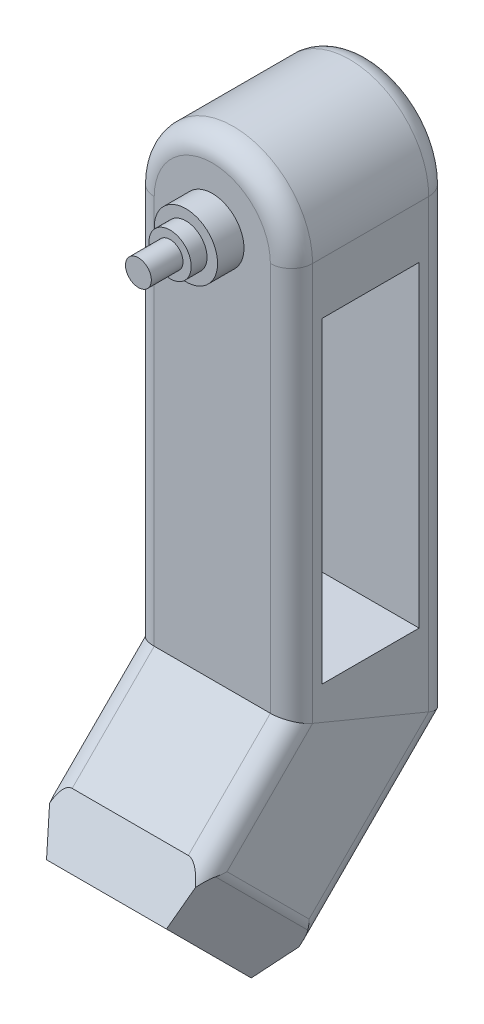
SolidWorks part; units mm, degrees
ref_plane "Front Plane" through (0, 0, 0) normal (0, 0, 1) x (1, 0, 0)
ref_plane "Top Plane" through (0, 0, 0) normal (0, 1, 0) x (1, 0, 0)
ref_plane "Right Plane" through (0, 0, 0) normal (1, 0, 0) x (0, 0, -1)
ref_plane "Plane2" through (0, 96.393, 0) normal (0, 1, 0) x (1, 0, 0)
sketch "Sketch10" plane through (0, 0, 0) normal (1, 0, 0) x (0, 0, -1)
  line L0 (0, 96.393) -> (0, -5.207)
  line L1 (55, 96.393) -> (-55, 96.393) construction
  line L2 (0, -5.207) -> (-25.3243, -30.5313)
  dimension "D1" = 101.6
  dimension "D2" = 35.814
  dimension "D3" = 135
sketch "Sketch11" plane through (0, 96.393, 0) normal (0, 1, 0) x (1, 0, 0)
  line L1 (-19.05, -19.05) -> (19.05, -19.05)
  line L2 (-19.05, -19.05) -> (-19.05, 19.05)
  line L3 (-19.05, 19.05) -> (19.05, 19.05)
  line L4 (19.05, -19.05) -> (19.05, 19.05)
  line L5 (-19.05, -19.05) -> (19.05, 19.05) construction
  line L6 (-19.05, 19.05) -> (19.05, -19.05) construction
  point P0 (0, 0)
  dimension "D1" = 38.1
sweep "Sweep1" add profiles "Sketch11" path "Sketch10"
sketch "Sketch12" plane through (0, -27.9278, 27.9278) normal (0, -0.7071, 0.7071) x (1, 0, 0)
  line L4 (19.05, -22.7319) -> (19.05, 15.3681)
  line L5 (19.05, -22.7319) -> (19.05, 15.3681)
  line L6 (19.05, 15.3681) -> (-19.05, 15.3681)
  line L7 (19.05, 15.3681) -> (-19.05, 15.3681)
  line L8 (-19.05, 15.3681) -> (-19.05, -22.7319)
  line L9 (-19.05, 15.3681) -> (-19.05, -22.7319)
  line L10 (-19.05, -22.7319) -> (19.05, -22.7319)
  line L11 (-19.05, -22.7319) -> (19.05, -22.7319)
  dimension "D1" = 0
extrude "Boss-Extrude5" add sketch "Sketch12" along normal blind 12.7 draft 20
sketch "Sketch13" plane through (0, 0, -19.05) normal (0, 0, -1) x (-1, 0, 0)
  line L0 (20.955, 96.393) -> (-20.955, 96.393) construction
  line L1 (0, 31.8146) -> (0, -31.8146) construction
  line L2 (-19.05, 96.393) -> (19.05, 96.393)
  arc A0 (19.05, 96.393) -> (-19.05, 96.393) centre (0, 96.393) ccw
  dimension "D1" = 38.1
extrude "Boss-Extrude6" add sketch "Sketch13" against normal up to surface (38.1 mm away) up to face at (0, 49.5384, 19.05)
sketch "Sketch15" plane through (0, -36.9081, 36.9081) normal (0, -0.7071, 0.7071) x (1, 0, 0)
  line L1 (-14.4276, 10.7457) -> (14.4276, -18.1095) construction
  line L2 (-14.4276, -18.1095) -> (14.4276, 10.7457) construction
  circle A2 centre (0, -3.6819) radius 12.065
  dimension "D1" = 24.13
extrude "Cut-Extrude3" cut sketch "Sketch15" against normal blind 25.4
sketch "Sketch16" plane through (19.05, 0, 0) normal (1, 0, 0) x (0, 0, -1)
  line L0 (0, 96.393) -> (0, 0) construction
  line L1 (-19.05, 96.393) -> (19.05, 96.393) construction
  line L2 (-19.05, 49.5384) -> (19.05, 49.5384) construction
  line L3 (-19.05, 96.393) -> (-19.05, 2.6838) construction
  line L4 (19.05, 96.393) -> (19.05, -13.0978) construction
  line L5 (-11.6553, 83.82) -> (11.6553, 83.82)
  line L6 (11.6553, 83.82) -> (11.6553, 7.62)
  line L7 (11.6553, 7.62) -> (-11.6553, 7.62)
  line L8 (-11.6553, 7.62) -> (-11.6553, 83.82)
  point P13 (0, 83.82)
  dimension "D1" = 90
  dimension "D2" = 90
  dimension "D3" = 90
  dimension "D4" = 90
  dimension "D5" = 76.2
  dimension "D6" = 23.3106
  dimension "D7" = 23.3106
  dimension "D8" = 83.82
extrude "Cut-Extrude4" cut sketch "Sketch16" against normal blind 59.8307
sketch "Sketch17" plane through (0, 0, 19.05) normal (0, 0, 1) x (1, 0, 0)
  line L0 (0, 115.443) -> (0, 96.393) construction
  line L1 (-19.05, 96.393) -> (19.05, 96.393) construction
  arc A0 (19.05, 96.393) -> (-19.05, 96.393) centre (0, 96.393) ccw construction
  circle A1 centre (0, 96.393) radius 7.62
  dimension "D1" = 15.24
extrude "Boss-Extrude7" add sketch "Sketch17" along normal blind 6.35
sketch "Sketch18" plane through (0, 0, 25.4) normal (0, 0, 1) x (1, 0, 0)
  circle A0 centre (0, 96.393) radius 5.08
  dimension "D1" = 10.16
extrude "Boss-Extrude8" add sketch "Sketch18" along normal blind 3.81
sketch "Sketch19" plane through (0, 0, 29.21) normal (0, 0, 1) x (1, 0, 0)
  circle A0 centre (0, 96.393) radius 3.1115
  dimension "D1" = 6.223
extrude "Boss-Extrude9" add sketch "Sketch19" along normal blind 7.62
fillet "Fillet2" radius 5.08 12 edges at (19.05, 41.6476, -19.05) (0, 115.443, -19.05) (19.05, 49.5384, 19.05) (0, 115.443, 19.05) (-19.05, -7.1886, 28.9224) (-19.05, -30.5313, 25.3243) (-19.05, -28.5497, -3.598) (-19.05, 41.6476, -19.05) (-19.05, 49.5384, 19.05) (19.05, -30.5313, 25.3243) (19.05, -28.5497, -3.598) (19.05, -7.1886, 28.9224)
